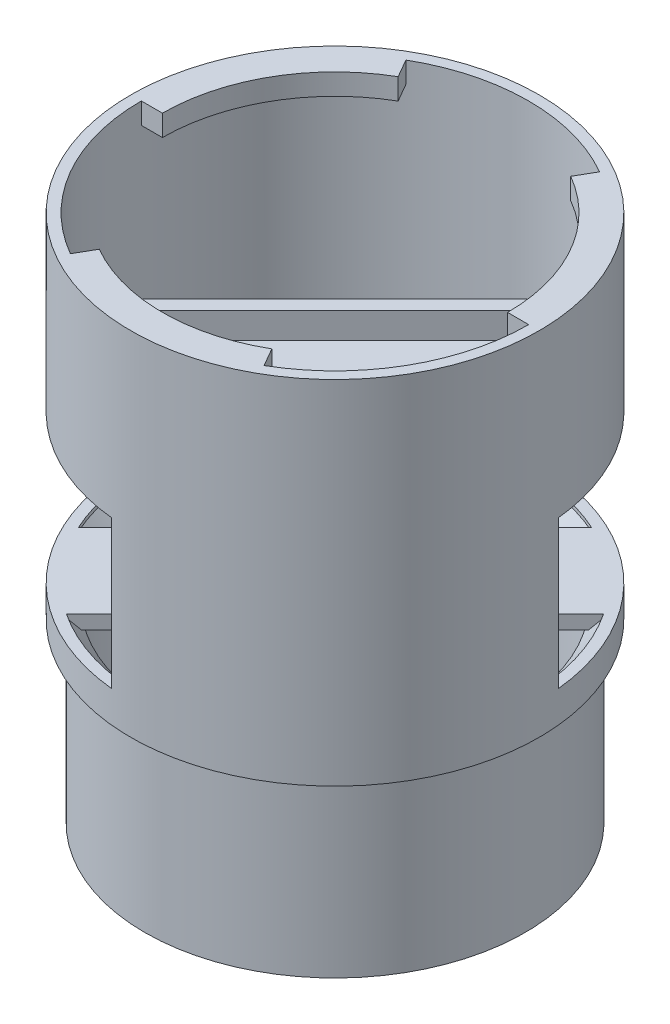
SolidWorks part; units mm, degrees
ref_plane "Front Plane" through (0, 0, 0) normal (0, 0, 1) x (1, 0, 0)
ref_plane "Top Plane" through (0, 0, 0) normal (0, 1, 0) x (1, 0, 0)
ref_plane "Right Plane" through (0, 0, 0) normal (1, 0, 0) x (0, 0, -1)
sketch "Sketch1" plane through (0, 0, 0) normal (0, 1, 0) x (1, 0, 0)
  circle A0 centre (0, 0) radius 25.5
  circle A1 centre (0, 0) radius 27
  dimension "D1" = 54
  dimension "D2" = 1.5
extrude "Boss-Extrude3" add sketch "Sketch1" along normal blind 25
sketch "Sketch3" plane through (0, 0, 0) normal (0, -1, 0) x (1, 0, 0)
  line L0 (-25.5, 0) -> (25.5, 0) construction
  line L1 (0, 25.5) -> (0, -25.5) construction
  line L2 (-25.1843, 4) -> (-14.4568, 4)
  line L3 (-4, 14.4568) -> (-4, 25.1843)
  line L4 (14.4568, 4) -> (25.1843, 4)
  line L5 (4, 25.1843) -> (4, 14.4568)
  line L6 (4, -14.4568) -> (4, -25.1843)
  line L7 (25.1843, -4) -> (14.4568, -4)
  line L8 (-14.4568, -4) -> (-25.1843, -4)
  line L9 (-4, -25.1843) -> (-4, -14.4568)
  circle A0 centre (0, 0) radius 25.5 construction
  arc A1 (-25.1843, 4) -> (-25.1843, -4) centre (0, 0) ccw
  arc A2 (4, 25.1843) -> (-4, 25.1843) centre (0, 0) ccw
  arc A3 (25.1843, -4) -> (25.1843, 4) centre (0, 0) ccw
  arc A4 (-4, -25.1843) -> (4, -25.1843) centre (0, 0) ccw
  circle A5 centre (-10, 0) radius 1.75
  circle A6 centre (0, 10) radius 1.75
  circle A7 centre (10, 0) radius 1.75
  circle A8 centre (0, -10) radius 1.75
  circle A9 centre (0, 0) radius 5
  arc A10 (-14.4568, -4) -> (-4, -14.4568) centre (0, 0) ccw
  arc A11 (-4, 14.4568) -> (-14.4568, 4) centre (0, 0) ccw
  arc A12 (14.4568, 4) -> (4, 14.4568) centre (0, 0) ccw
  arc A13 (4, -14.4568) -> (14.4568, -4) centre (0, 0) ccw
  point P22 (0, 0)
  point P32 (0, 0)
  dimension "D4" = 3.5
  dimension "D7" = 10
  dimension "D8" = 30
  dimension "D1" = 4
  dimension "D2" = 4
  dimension "D5" = 10
  dimension "D3" = 4
  dimension "D6" = 4
extrude "Boss-Extrude4" add sketch "Sketch3" against normal blind 6
ref_plane "Plane1" through (0, 0, 0) normal (-0.7071, 0, 0.7071) x (0.7071, 0, 0.7071)
sketch "Sketch4" plane through (0, 0, 0) normal (-0.7071, 0, 0.7071) x (0.7071, 0, 0.7071)
  line L0 (0, 0) -> (0, 105.4419) construction
  line L1 (-27, 25) -> (-29, 25)
  line L2 (27, 25) -> (-27, 25) construction
  line L3 (-20.2823, 75) -> (15.9379, 75) construction
  line L4 (25.5, 25) -> (-25.5, 25) construction
  line L5 (-29, 25) -> (-29, 75)
  line L6 (-29, 75) -> (-27.5, 75)
  line L7 (-27.5, 75) -> (-27.5, 29)
  line L8 (-27.5, 29) -> (-25.5, 27)
  line L9 (-29, 41.2871) -> (-29, 82.0597) construction
  line L10 (-25.5, 27) -> (-25.5, 25)
  line L11 (-25.5, 25) -> (-27, 25)
  line L15 (0, 75) -> (0, 73.5)
  line L16 (0, 75) -> (0, 73.5)
  point P16 (-25.5, 25)
  dimension "D1" = 50
  dimension "D2" = 29
  dimension "D3" = 1.5
  dimension "D4" = 50
  dimension "D5" = 2
  dimension "D6" = 135
revolve "Revolve1" add sketch "Sketch4" angle 360 about L0
sketch "Sketch5" plane through (0, 0, 0) normal (-0.7071, 0, 0.7071) x (0.7071, 0, 0.7071)
  line L0 (0, 82.5379) -> (0.5211, 25.5117) construction
  line L2 (-17.6113, 29.5) -> (18.3887, 29.5)
  line L3 (-17.6113, 29.5) -> (-17.6113, 50.5)
  line L4 (-17.6113, 50.5) -> (18.3887, 50.5)
  line L5 (18.3887, 29.5) -> (18.3887, 50.5)
  line L6 (-17.6113, 29.5) -> (18.3887, 50.5) construction
  line L7 (-17.6113, 50.5) -> (18.3887, 29.5) construction
  line L8 (27.5, 29) -> (-27.5, 29) construction
  point P2 (0.3887, 40)
  dimension "D1" = 11
  dimension "D2" = 21
  dimension "D3" = 36
extrude "Cut-Extrude1" cut sketch "Sketch5" against normal through all both and the other way through all
sketch "Sketch6" plane through (0, 0, 0) normal (-0.7071, 0, 0.7071) x (0.7071, 0, 0.7071)
  line L2 (-17.6113, 50.5) -> (18.3887, 50.5) construction
  line L6 (-19.6113, 29.5) -> (-17.6113, 29.5)
  line L8 (-9.6113, 29.5) -> (5.3887, 29.5)
  line L9 (5.3887, 29.5) -> (5.3887, 27.5)
  line L10 (5.3887, 27.5) -> (-9.6113, 27.5)
  line L11 (-9.6113, 27.5) -> (-9.6113, 29.5)
  line L14 (-17.6113, 29.5) -> (-17.6113, 50.5)
  line L15 (-17.6113, 50.5) -> (-19.6113, 50.5)
  line L16 (-19.6113, 50.5) -> (-19.6113, 29.5)
  line L17 (-9.6113, 50.5) -> (-9.6113, 52.5)
  line L19 (-9.6113, 52.5) -> (5.83, 52.5)
  line L20 (5.83, 52.5) -> (5.83, 50.5)
  line L21 (5.83, 50.5) -> (-9.6113, 50.5)
  dimension "D1" = 2
  dimension "D2" = 2
  dimension "D3" = 21
  dimension "D4" = 2
  dimension "D5" = 15
  dimension "D6" = 8
extrude "Boss-Extrude6" add sketch "Sketch6" against normal up to next and the other way up to next
sketch "Sketch7" plane through (0, 75, 0) normal (0, 1, 0) x (1, 0, 0)
  line L0 (-29, 0) -> (29, 0) construction
  line L1 (-27.5, 0) -> (-24.5, 0)
  line L2 (-12.25, 21.2176) -> (-13.75, 23.8157)
  circle A0 centre (0, 0) radius 29 construction
  arc A1 (-13.75, 23.8157) -> (-27.5, 0) centre (0, 0) ccw
  arc A2 (-12.25, 21.2176) -> (-24.5, 0) centre (0, 0) ccw
  circle A3 centre (0, 0) radius 24.5 construction
  circle A4 centre (0, 0) radius 27.5 construction
  dimension "D2" = 60
  dimension "D1" = 3
extrude "Boss-Extrude7" add sketch "Sketch7" against normal blind 3
ref_axis "Axis1" through (0, 75, 0) along (0, -1, 0)
pattern_circular "CirPattern1" count 3 over 360 about axis through (0, 75, 0) along (0, -1, 0) of "Boss-Extrude7"
fillet "Fillet1" radius 10 4 edges at (0, 6, 25.5) (-25.5, 6, 0) (0, 6, -25.5) (25.5, 6, 0)
